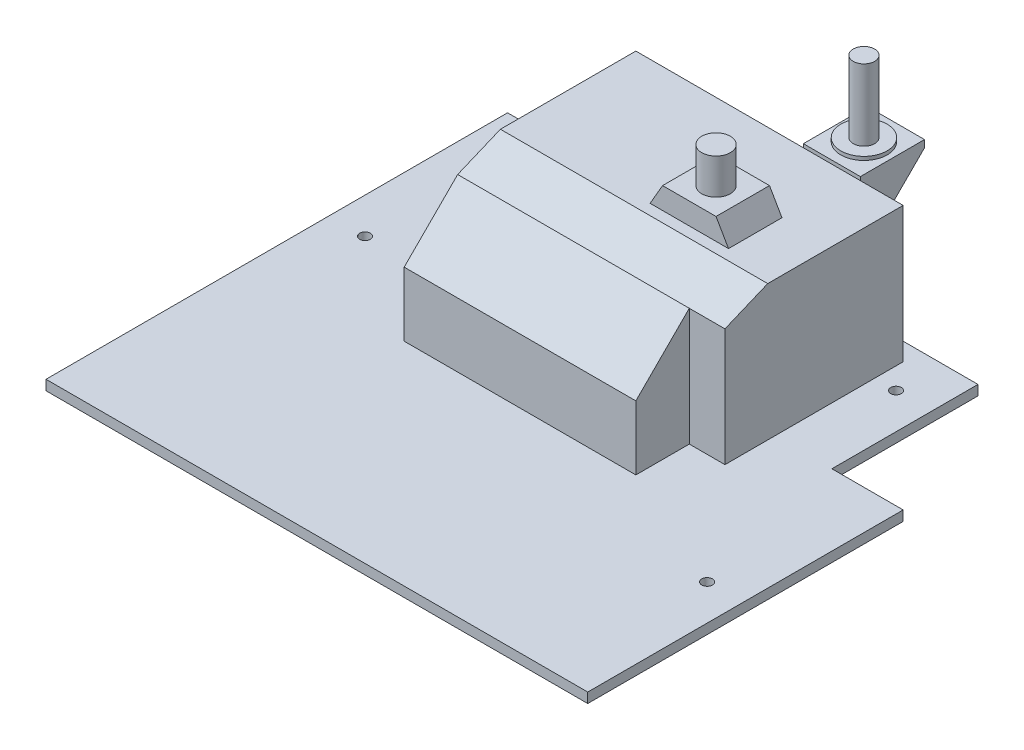
SolidWorks part; units mm, degrees
ref_plane "Front" through (0, 0, 0) normal (0, 0, 1) x (1, 0, 0)
ref_plane "Top" through (0, 0, 0) normal (0, 1, 0) x (1, 0, 0)
ref_plane "Right" through (0, 0, 0) normal (1, 0, 0) x (0, 0, -1)
sketch "Sketch1" plane through (0, 0, 0) normal (0, 1, 0) x (1, 0, 0)
  line L0 (56, 64.75) -> (56, 23.75)
  line L1 (-76, -64.75) -> (76, -64.75)
  line L2 (-76, -64.75) -> (-76, 64.75)
  line L3 (-76, 64.75) -> (76, 64.75)
  line L4 (76, -64.75) -> (76, 64.75)
  line L5 (-76, -64.75) -> (76, 64.75) construction
  line L6 (-76, 64.75) -> (76, -64.75) construction
  line L7 (56, 23.75) -> (76, 23.75)
  circle A0 centre (46, 51.75) radius 1.5
  circle A1 centre (-46, 51.75) radius 1.5
  circle A2 centre (-66, 14.75) radius 1.5
  circle A3 centre (66, -21.25) radius 1.5
  point P0 (0, 0)
  dimension "D5" = 3
  dimension "D8" = 3
  dimension "D9" = 30
  dimension "D10" = 3
  dimension "D12" = 50
  dimension "D13" = 3
  dimension "D14" = 10
  dimension "D15" = 45
  dimension "D1" = 129.5
  dimension "D2" = 152
  dimension "D3" = 20
  dimension "D4" = 41
  dimension "D6" = 13
  dimension "D7" = 10
  dimension "D11" = 10
extrude "Boss-Extrude1" add sketch "Sketch1" along normal blind 2.8 contours L7 L0 L3 L2 L1 L4 A3 A2 A1 A0 region at (-2.8733, 0, 1.9628)
sketch "Sketch2" plane through (0, 2.8, 0) normal (0, 1, 0) x (1, 0, 0)
  line L0 (-76, 64.75) -> (56, 64.75) construction
  line L1 (-35, -5.25) -> (40, -5.25)
  line L2 (-35, -5.25) -> (-35, 59.75)
  line L3 (-35, 59.75) -> (40, 59.75)
  line L4 (40, -5.25) -> (40, 59.75)
  line L5 (-35, -5.25) -> (40, 59.75) construction
  line L6 (-35, 59.75) -> (40, -5.25) construction
  line L8 (40, -5.25) -> (30, -5.25)
  line L9 (40, -5.25) -> (40, 9.75)
  line L10 (40, 9.75) -> (30, 9.75)
  line L11 (30, -5.25) -> (30, 9.75)
  line L12 (40, -5.25) -> (30, 9.75) construction
  line L13 (40, 9.75) -> (30, -5.25) construction
  circle A0 centre (46, 51.75) radius 1.5 construction
  point P0 (2.5, 27.25)
  point P12 (35, 2.25)
  dimension "D1" = 65
  dimension "D2" = 75
  dimension "D3" = 5
  dimension "D4" = 15
  dimension "D5" = 10
  dimension "D6" = 6
extrude "Boss-Extrude2" add sketch "Sketch2" along normal blind 38 contours L1 L11 L10 L4 L3 L2 region at (1.4683, 2.8, -28.0437)
sketch "Sketch3" plane through (-35, 0, 0) normal (-1, 0, 0) x (0, 0, 1)
  line L0 (5.25, 20.8) -> (-9.75, 35.8)
  line L1 (5.25, 40.8) -> (5.25, 2.8) construction
  line L2 (-9.75, 35.8) -> (-21.75, 40.8)
  line L3 (5.25, 40.8) -> (-59.75, 40.8) construction
  line L4 (-21.75, 40.8) -> (5.25, 40.8)
  line L5 (5.25, 40.8) -> (5.25, 20.8)
  dimension "D1" = 15
  dimension "D2" = 45
  dimension "D3" = 12
  dimension "D4" = 5
extrude "Cut-Extrude1" cut sketch "Sketch3" against normal up to next
sketch "Sketch4" plane through (0, 0, -59.75) normal (0, 0, -1) x (-1, 0, 0)
  line L1 (-28, 41.8) -> (-12, 41.8)
  line L2 (-28, 41.8) -> (-28, 21.8)
  line L3 (-28, 21.8) -> (-12, 21.8)
  line L4 (-12, 41.8) -> (-12, 21.8)
  line L5 (-28, 41.8) -> (-12, 21.8) construction
  line L6 (-28, 21.8) -> (-12, 41.8) construction
  line L7 (-40, 40.8) -> (-40, 2.8) construction
  line L8 (35, 40.8) -> (-40, 40.8) construction
  point P4 (-20, 31.8)
  dimension "D1" = 20
  dimension "D2" = 16
  dimension "D3" = 20
  dimension "D4" = 1
extrude "Boss-Extrude3" add sketch "Sketch4" along normal blind 18
chamfer "Chamfer1" distance 18 angle 45 1 edges at (20, 21.8, -77.75)
sketch "Sketch5" plane through (0, 41.8, 0) normal (0, 1, 0) x (1, 0, 0)
  line L0 (28, 77.75) -> (12, 59.75) construction
  circle A0 centre (20, 68.75) radius 6.5
  dimension "D1" = 13
extrude "Boss-Extrude4" add sketch "Sketch5" along normal blind 1
sketch "Sketch6" plane through (0, 42.8, 0) normal (0, 1, 0) x (1, 0, 0)
  circle A0 centre (20, 68.75) radius 3
  dimension "D1" = 6
extrude "Boss-Extrude5" add sketch "Sketch6" along normal blind 20
ref_plane "Plane1" through (0, 0, -24.75) normal (0, 0, 1) x (1, 0, 0)
sketch "Sketch7" plane through (0, 0, -24.75) normal (0, 0, 1) x (1, 0, 0)
  line L0 (26, 40.8) -> (4, 40.8)
  line L1 (40, 40.8) -> (-35, 40.8) construction
  line L2 (4, 40.8) -> (7.5, 46.8622)
  line L3 (7.5, 46.8622) -> (22.5, 46.8622)
  line L4 (22.5, 46.8622) -> (26, 40.8)
  line L5 (40, 35.8) -> (40, 40.8) construction
  dimension "D1" = 22
  dimension "D2" = 60
  dimension "D3" = 15
  dimension "D4" = 60
  dimension "D5" = 14
extrude "Boss-Extrude6" add sketch "Sketch7" against normal blind 15
sketch "Sketch8" plane through (0, 46.8622, 0) normal (0, 1, 0) x (1, 0, 0)
  line L0 (7.5, 39.75) -> (22.5, 24.75) construction
  circle A0 centre (15, 32.25) radius 4
  dimension "D1" = 8
extrude "Boss-Extrude7" add sketch "Sketch8" along normal blind 10
